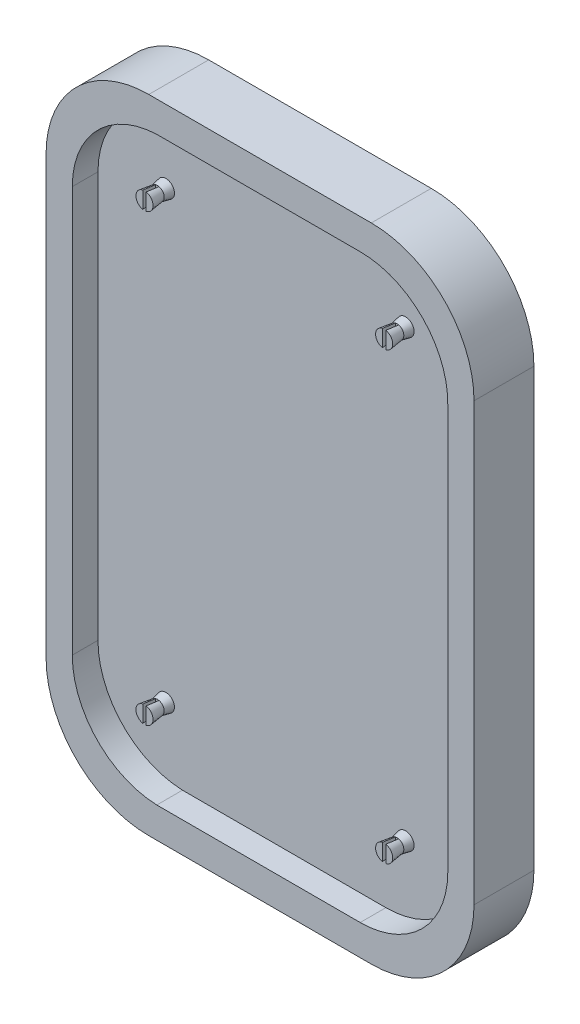
SolidWorks part; units mm, degrees
ref_plane "Front Plane" through (0, 0, 0) normal (0, 0, 1) x (1, 0, 0)
ref_plane "Top Plane" through (0, 0, 0) normal (0, 1, 0) x (1, 0, 0)
ref_plane "Right Plane" through (0, 0, 0) normal (1, 0, 0) x (0, 0, -1)
sketch "Sketch1" plane through (0, 0, 0) normal (0, 0, 1) x (1, 0, 0)
  line L1 (-31.75, 47.625) -> (31.75, 47.625)
  line L2 (-31.75, 47.625) -> (-31.75, -47.625)
  line L3 (-31.75, -47.625) -> (31.75, -47.625)
  line L4 (31.75, 47.625) -> (31.75, -47.625)
  line L5 (-31.75, 47.625) -> (31.75, -47.625) construction
  line L6 (-31.75, -47.625) -> (31.75, 47.625) construction
  point P0 (0, 0)
  dimension "D1" = 95.25
  dimension "D2" = 63.5
extrude "Boss-Extrude1" add sketch "Sketch1" against normal blind 8.89
sketch "Sketch2" plane through (0, 0, 0) normal (0, 0, 1) x (1, 0, 0)
  line L0 (22.86, 30.1) -> (22.86, -30.1) construction
  line L1 (14.86, -38.1) -> (-14.86, -38.1) construction
  line L2 (-22.86, -30.1) -> (-22.86, 30.1) construction
  line L3 (-14.86, 38.1) -> (14.86, 38.1) construction
  line L4 (22.86, 30.1) -> (22.86, -30.1) construction
  line L5 (14.86, -38.1) -> (-14.86, -38.1) construction
  line L6 (-22.86, -30.1) -> (-22.86, 30.1) construction
  line L7 (-14.86, 38.1) -> (14.86, 38.1) construction
  line L8 (27.86, 30.1) -> (27.86, -30.1) construction
  line L9 (14.86, -43.1) -> (-14.8586, -43.1) construction
  line L10 (-27.86, -30.1) -> (-27.86, 30.0986) construction
  line L11 (-14.86, 43.1) -> (14.8586, 43.1) construction
  arc A0 (14.86, -38.1) -> (22.86, -30.1) centre (14.86, -30.1) ccw construction
  circle A1 centre (-17.78, 33.02) radius 1.1
  circle A2 centre (-17.78, 33.02) radius 1.1 construction
  circle A3 centre (17.78, 33.02) radius 1.1
  circle A4 centre (17.78, 33.02) radius 1.1 construction
  circle A5 centre (17.78, -33.02) radius 1.1
  circle A6 centre (17.78, -33.02) radius 1.1 construction
  circle A7 centre (-17.78, -33.02) radius 1.1
  circle A8 centre (-17.78, -33.02) radius 1.1 construction
  arc A9 (-22.8575, -30.3856) -> (-14.86, -38.1) centre (-14.8645, -30.102) ccw construction
  arc A10 (-15.1456, 38.0975) -> (-22.86, 30.1) centre (-14.862, 30.1045) ccw construction
  arc A11 (22.8575, 30.3856) -> (14.86, 38.1) centre (14.8645, 30.102) ccw construction
  arc A12 (14.86, -38.1) -> (22.86, -30.1) centre (14.86, -30.1) ccw construction
  arc A13 (-22.8575, -30.3856) -> (-14.86, -38.1) centre (-14.8645, -30.102) ccw construction
  arc A14 (-15.1456, 38.0975) -> (-22.86, 30.1) centre (-14.862, 30.1045) ccw construction
  arc A15 (22.8575, 30.3856) -> (14.86, 38.1) centre (14.8645, 30.102) ccw construction
  arc A16 (14.86, -43.1) -> (27.86, -30.1) centre (14.86, -30.1) ccw construction
  arc A17 (-27.8543, -30.5629) -> (-14.8586, -43.1) centre (-14.8645, -30.102) ccw construction
  arc A18 (-15.3229, 43.0943) -> (-27.86, 30.0986) centre (-14.862, 30.1045) ccw construction
  arc A19 (27.8543, 30.5629) -> (14.8586, 43.1) centre (14.8645, 30.102) ccw construction
  dimension "D1" = 0
  dimension "D2" = 0
  dimension "D3" = 0
  dimension "D4" = 0
  dimension "D5" = 5
sketch "Sketch4" plane through (0, 0, 0) normal (0, 0, 1) x (1, 0, 0)
  line L0 (-27.86, -30.1) -> (-27.86, 30.0986) construction
  line L1 (27.86, 30.1) -> (27.86, -30.1) construction
  line L2 (-15.3215, -43.0895) -> (14.86, -43.1)
  line L3 (27.86, 29.848) -> (27.86, -30.1)
  line L4 (-27.86, -30.1) -> (-27.86, 30.1045)
  line L5 (-15.3229, 43.0943) -> (14.8586, 43.1)
  line L7 (14.86, -43.1) -> (-14.8586, -43.1) construction
  arc A0 (-15.3229, 43.0943) -> (-27.86, 30.1045) centre (-14.862, 30.1045) ccw
  arc A1 (14.8586, 43.1) -> (27.86, 29.848) centre (14.8645, 30.102) cw
  arc A2 (-27.86, -30.1) -> (-15.3215, -43.0895) centre (-14.8645, -30.102) ccw
  arc A3 (27.86, -30.1) -> (14.86, -43.1) centre (14.86, -30.1) cw
  arc A4 (14.86, -43.1) -> (27.86, -30.1) centre (14.86, -30.1) ccw construction
  point P27 (-14.8586, -43.1)
  point P28 (14.86, -43.1)
extrude "Cut-Extrude1" cut sketch "Sketch4" against normal blind 3.81
ref_axis "Axis1" through (-17.78, 33.02, -19.7096) along (0, 0, 1)
sketch "Sketch7" plane through (0, 0, 0) normal (0, 1, 0) x (1, 0, 0)
  line L1 (-17.78, 3.81) -> (-17.78, 0) construction
  line L2 (-17.78, 19.7096) -> (-17.78, -16.4475) construction
  line L3 (-27.86, 3.81) -> (-15.3229, 3.81) construction
  line L4 (-16.51, 3.81) -> (-16.764, 2.54)
  line L5 (-16.764, 2.54) -> (-16.51, 0.635)
  line L6 (-16.51, 0.635) -> (-17.78, 0.635)
  line L8 (-16.51, 3.81) -> (-17.78, 3.81)
  line L9 (-17.78, 3.81) -> (-17.78, 2.921)
  line L10 (-17.78, 2.921) -> (-17.78, 0.635)
  line L11 (-27.86, 0) -> (-15.3229, 0) construction
  point P4 (-17.526, 1.764)
  point P11 (-17.78, 2.794)
  point P13 (-17.78, 2.7141)
  point P14 (0, 0)
  point P15 (0, 0)
  point P16 (-17.78, 0)
  point P19 (-17.78, 2.8545)
  point P20 (-17.526, 1.4168)
  point P21 (-17.526, 1.4586)
  point P22 (-17.526, 1.2319)
  point P23 (-17.4999, 1.27)
  point P24 (-17.78, 1.27)
  dimension "D1" = 1.27
  dimension "D2" = 1.016
  dimension "D3" = 1.27
  dimension "D4" = 0.889
  dimension "D5" = 1.27
  dimension "D6" = 1.905
ref_plane "Plane1" through (0, 33.02, 0) normal (0, 1, 0) x (0, 0, 1)
sketch "Sketch8" plane through (0, 33.02, 0) normal (0, 1, 0) x (0, 0, 1)
  line L0 (-3.81, -17.78) -> (-2.921, -17.78) construction
  line L1 (-2.921, -17.78) -> (-0.635, -17.78) construction
  line L2 (-0.635, -16.51) -> (-0.635, -17.78) construction
  line L3 (-2.54, -16.764) -> (-0.635, -16.51) construction
  line L4 (-3.81, -16.51) -> (-2.54, -16.764) construction
  line L5 (-3.81, -16.51) -> (-3.81, -17.78) construction
  line L6 (-3.81, -17.78) -> (-2.921, -17.78)
  line L7 (-2.921, -17.78) -> (-0.635, -17.78)
  line L8 (-0.635, -16.51) -> (-0.635, -17.78)
  line L9 (-2.54, -16.764) -> (-0.635, -16.51)
  line L10 (-3.81, -16.51) -> (-2.54, -16.764)
  line L11 (-3.81, -16.51) -> (-3.81, -17.78)
  line L12 (-3.81, -17.78) -> (0, -17.78) construction
revolve "Revolve1" add sketch "Sketch8" angle 360 about L12
sketch "Sketch9" plane through (0, 33.02, 0) normal (0, 1, 0) x (0, 0, 1)
  line L12 (-3.81, 17.78) -> (0, 17.78) construction
  line L13 (-3.81, 17.78) -> (-2.54, 17.78)
  line L14 (-2.54, 17.78) -> (-0.635, 17.78)
  line L15 (-0.635, 19.05) -> (-0.635, 17.78)
  line L16 (-2.54, 18.796) -> (-0.635, 19.05)
  line L17 (-3.81, 19.05) -> (-2.54, 18.796)
  line L18 (-3.81, 19.05) -> (-3.81, 17.78)
  point P1 (0, -17.78)
  point P2 (0, -17.78)
  point P3 (0, -17.78)
  point P4 (0.1407, -15.3505)
  point P6 (0, -3.5548)
  point P8 (0, 17.78)
  point P9 (-0.635, 17.78)
  point P10 (-2.4505, 18.796)
  point P12 (-2.54, 17.78)
  point P18 (0, 0)
  dimension "D1" = 1.016
  dimension "D2" = 1.27
  dimension "D3" = 1.27
  dimension "D4" = 1.27
  dimension "D5" = 1.905
  dimension "D6" = 3.81
revolve "Revolve2" add sketch "Sketch9" angle 360 about L12
mirror "Mirror1" about plane through (0, 0, 0) normal (0, 1, 0) of "Revolve2", "Revolve1"
sketch "Sketch10" plane through (0, 0, -0.635) normal (0, 0, 1) x (1, 0, 0)
  line L0 (-17.78, 31.75) -> (-17.78, 34.29) construction
  line L1 (-17.53, 31.7748) -> (-17.53, 34.2652)
  line L2 (-18.03, 31.7748) -> (-18.03, 34.2652)
  line L3 (-18.03, 31.75) -> (-18.03, 34.29) construction
  line L4 (-17.53, 31.75) -> (-17.53, 34.29) construction
  circle A0 centre (-17.78, 33.02) radius 1.27 construction
  arc A1 (-18.03, 31.7748) -> (-17.53, 31.7748) centre (-17.78, 33.02) ccw
  arc A2 (-17.53, 34.2652) -> (-18.03, 34.2652) centre (-17.78, 33.02) ccw
  dimension "D1" = 0.25
  dimension "D2" = 0.25
extrude "Cut-Extrude2" cut sketch "Sketch10" against normal blind 1.905
mirror "Mirror2" about plane through (0, 0, 0) normal (0, 1, 0) of "Cut-Extrude2" second plane through (0, 0, 0) second plane normal (1, 0, 0)
fillet "Fillet1" radius 15.24 4 edges at (31.75, -47.625, -4.445) (-31.75, -47.625, -4.445) (31.75, 47.625, -4.445) (-31.75, 47.625, -4.445)
